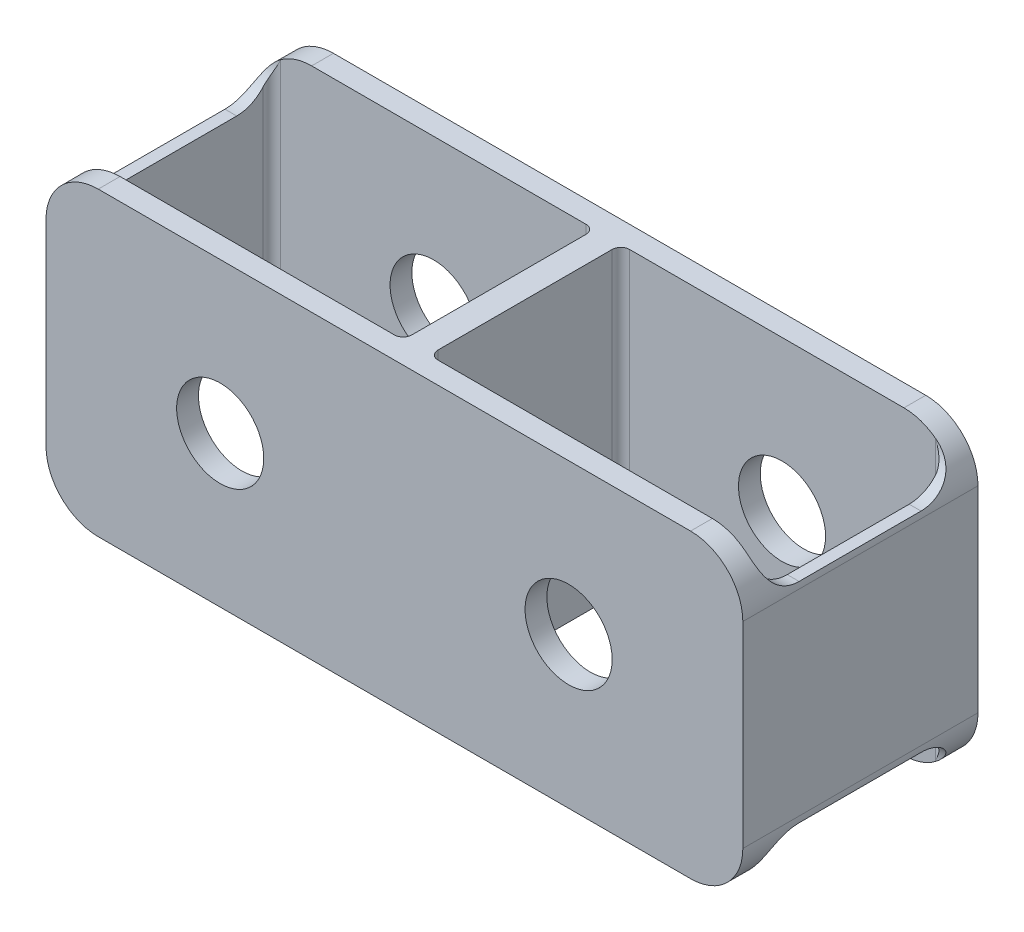
SolidWorks part; units mm, degrees
ref_plane "Front" through (0, 0, 0) normal (0, 0, 1) x (1, 0, 0)
ref_plane "Top" through (0, 0, 0) normal (0, 1, 0) x (1, 0, 0)
ref_plane "Right" through (0, 0, 0) normal (1, 0, 0) x (0, 0, -1)
sketch "Эскиз1" plane through (0, 0, 0) normal (0, 0, 1) x (1, 0, 0)
  line L0 (-10, 0) -> (10, 0) construction
  line L1 (-20, -8.6413) -> (20, -8.6413)
  line L2 (-20, -8.6413) -> (-20, 8.6413)
  line L3 (-20, 8.6413) -> (20, 8.6413)
  line L4 (20, -8.6413) -> (20, 8.6413)
  line L5 (-20, -8.6413) -> (20, 8.6413) construction
  line L6 (-20, 8.6413) -> (20, -8.6413) construction
  circle A0 centre (-10, 0) radius 2.5
  circle A1 centre (10, 0) radius 2.5
  point P4 (0, 0)
extrude "Бобышка-Вытянуть1" add sketch "Эскиз1" along normal blind 1.25
sketch "Эскиз2" plane through (0, 0, 1.25) normal (0, 0, 1) x (1, 0, 0)
  line L0 (20, 8.6413) -> (-20, 8.6413) construction
  line L1 (-0.75, -8.6413) -> (0.75, -8.6413)
  line L2 (-0.75, -8.6413) -> (-0.75, 8.6413)
  line L3 (-0.75, 8.6413) -> (0.75, 8.6413)
  line L4 (0.75, -8.6413) -> (0.75, 8.6413)
  line L5 (-0.75, -8.6413) -> (0.75, 8.6413) construction
  line L6 (-0.75, 8.6413) -> (0.75, -8.6413) construction
  line L7 (-20, 0) -> (-20, 6)
  line L8 (-20, 8.6413) -> (-20, -8.6413) construction
  line L9 (-20, 6) -> (-19.3, 6)
  line L10 (-19.3, 6) -> (-19.3, -6)
  line L11 (-19.3, -6) -> (-20, -6)
  line L12 (-20, -6) -> (-20, 0)
  line L13 (0, 8.6413) -> (0, -8.6413) construction
  line L14 (20, 6) -> (19.3, 6)
  line L15 (19.3, -6) -> (20, -6)
  line L16 (20, -6) -> (20, 0)
  line L17 (19.3, 6) -> (19.3, -6)
  line L18 (20, 0) -> (20, 6)
  circle A0 centre (-10, 0) radius 9 construction
  circle A1 centre (10, 0) radius 9 construction
  point P6 (0, 0)
  dimension "D1" = 6
  dimension "D2" = 6
  dimension "D3" = 1.5
  dimension "D4" = 0.7
extrude "Бобышка-Вытянуть2" add sketch "Эскиз2" along normal blind 11
sketch "Эскиз3" plane through (0, 0, 12.25) normal (0, 0, 1) x (1, 0, 0)
  line L0 (20, 6) -> (20, 8.6413) construction
  line L1 (-20, -8.6413) -> (20, -8.6413)
  line L2 (-20, -8.6413) -> (-20, 8.6413)
  line L3 (-20, 8.6413) -> (20, 8.6413)
  line L4 (20, -8.6413) -> (20, 8.6413)
  line L5 (-20, -8.6413) -> (20, 8.6413) construction
  line L6 (-20, 8.6413) -> (20, -8.6413) construction
  circle A0 centre (-10, 0) radius 2.5
  circle A1 centre (10, 0) radius 2.5
  point P0 (0, 0)
extrude "Бобышка-Вытянуть3" add sketch "Эскиз3" along normal blind 1.25
fillet "Скругление1" radius 0.5 8 edges at (-19.3, 0, 12.25) (19.3, 0, 12.25) (19.3, 0, 1.25) (-19.3, 0, 1.25) (-0.75, 0, 1.25) (0.75, 0, 1.25) (0.75, 0, 12.25) (-0.75, 0, 12.25)
fillet "Скругление2" radius 3 4 edges at (-20, -8.6413, 0.625) (-20, 8.6413, 0.625) (20, 8.6413, 12.875) (20, -8.6413, 12.875)
fillet "Скругление3" radius 2 8 edges at (-19.3892, -6, 12.25) (-19.3892, -6, 1.25) (-19.3892, 6, 1.25) (-19.3892, 6, 12.25) (19.3892, 6, 12.25) (19.3892, 6, 1.25) (19.3892, -6, 1.25) (19.3892, -6, 12.25)
